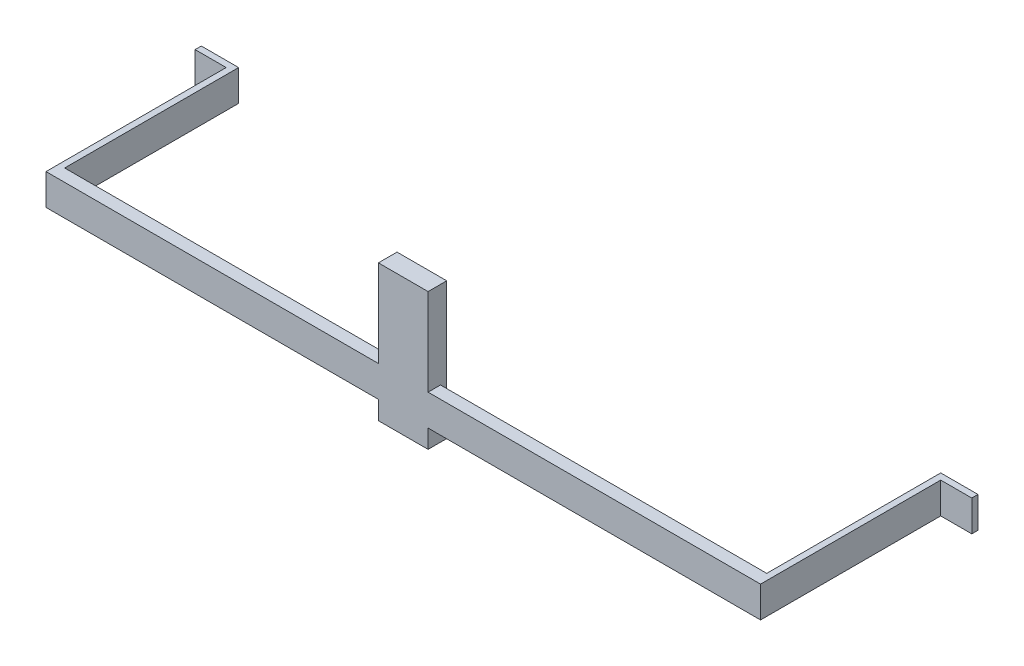
SolidWorks part; units mm, degrees
ref_plane "Front Plane" through (0, 0, 0) normal (0, 0, 1) x (1, 0, 0)
ref_plane "Top Plane" through (0, 0, 0) normal (0, 1, 0) x (1, 0, 0)
ref_plane "Right Plane" through (0, 0, 0) normal (1, 0, 0) x (0, 0, -1)
sketch "Sketch1" plane through (0, 0, 0) normal (0, 1, 0) x (1, 0, 0)
  line L0 (0, -55) -> (0, 55) construction
  line L1 (-57.5, -1) -> (57.5, -1)
  line L3 (-56.5, 1) -> (56.5, 1)
  line L8 (57.5, -1) -> (57.5, 28)
  line L11 (56.5, 29) -> (62.5, 29)
  line L13 (57.5, 28) -> (62.5, 28)
  line L14 (62.5, 29) -> (62.5, 28)
  line L15 (-57.5, -1) -> (-57.5, 28)
  line L16 (-62.5, 29) -> (-62.5, 28)
  line L17 (-57.5, 28) -> (-62.5, 28)
  line L19 (-56.5, 29) -> (-62.5, 29)
  line L20 (-56.5, 1) -> (-56.5, 29)
  line L22 (56.5, 1) -> (56.5, 29)
  point P0 (0, 0)
  dimension "D1" = 115
  dimension "D5" = 6
  dimension "D6" = 1
extrude "Boss-Extrude2" add sketch "Sketch1" along normal blind 5
sketch "Sketch3" plane through (0, 0, -1) normal (0, 0, -1) x (-1, 0, 0)
  line L0 (4.0055, 19.0254) -> (4.0055, -2.9746)
  line L5 (4.0055, -2.9746) -> (-3.9945, -2.9746)
  line L6 (3.0055, 18.0254) -> (-2.9945, 18.0254)
  line L7 (3.0055, 18.0254) -> (3.0055, -1.9746)
  line L8 (3.0055, -1.9746) -> (-2.9945, -1.9746)
  line L9 (-2.9945, 18.0254) -> (-2.9945, -1.9746)
  line L10 (-3.9945, 19.0254) -> (-3.9945, -2.9746)
  line L11 (4.0055, 19.0254) -> (-3.9945, 19.0254)
  point P9 (0, 1)
  dimension "D1" = 20
  dimension "D2" = 1
  dimension "D3" = 6
extrude "Boss-Extrude3" add sketch "Sketch3" along normal blind 1
sketch "Sketch5" plane through (0, 0, -1) normal (0, 0, 1) x (1, 0, 0)
  line L1 (-4.0055, 19.0254) -> (3.9945, 19.0254)
  line L2 (-4.0055, 19.0254) -> (-4.0055, -2.9746)
  line L3 (-4.0055, -2.9746) -> (3.9945, -2.9746)
  line L4 (3.9945, 19.0254) -> (3.9945, -2.9746)
extrude "Boss-Extrude5" add sketch "Sketch5" along normal up to surface (2 mm away) up to face at (0, 2.5, 1)
